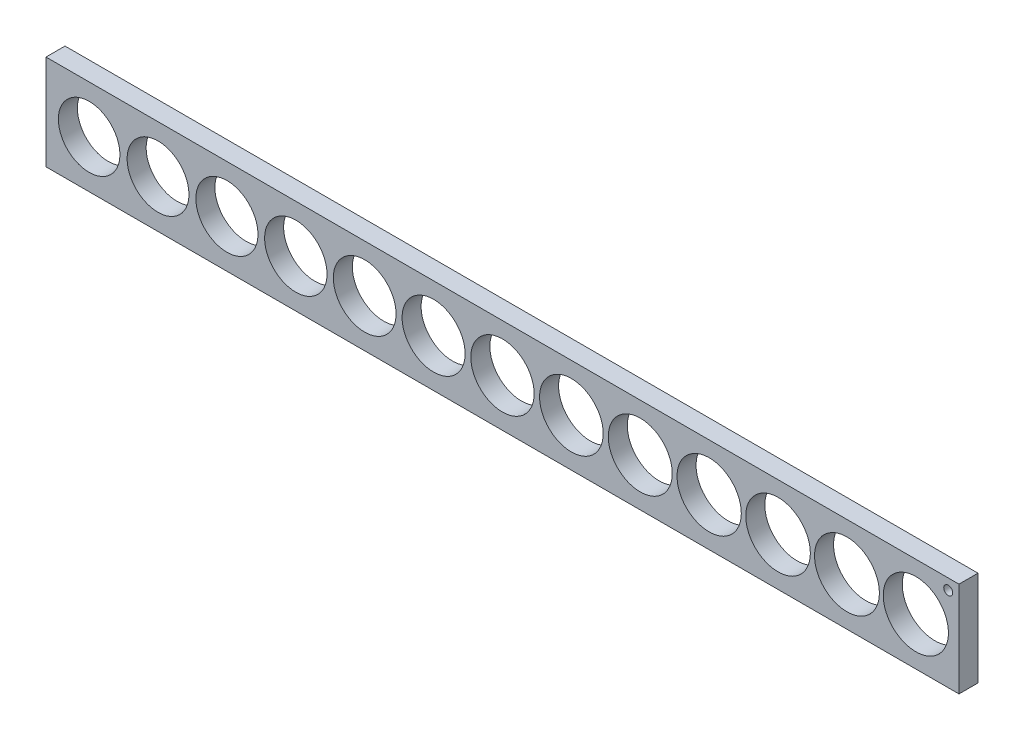
SolidWorks part; units mm, degrees
material "Custom Plastic"
ref_plane "X-Y Datum" through (0, 0, 0) normal (0, 0, 1) x (1, 0, 0)
ref_plane "X-Z Datum" through (0, 0, 0) normal (0, 1, 0) x (1, 0, 0)
ref_plane "Y-Z Datum" through (0, 0, 0) normal (1, 0, 0) x (0, 0, -1)
sketch "Sketch1" plane through (0, 0, 0) normal (0, 0, 1) x (1, 0, 0)
  line L0 (-152.4, 0) -> (152.4, 0) construction
  line L1 (-152.4, 15.875) -> (152.4, 15.875)
  line L2 (-152.4, 15.875) -> (-152.4, -15.875)
  line L3 (-152.4, -15.875) -> (152.4, -15.875)
  line L4 (152.4, 15.875) -> (152.4, -15.875)
  line L5 (-152.4, 15.875) -> (152.4, -15.875) construction
  line L6 (-152.4, -15.875) -> (152.4, 15.875) construction
  line L7 (0, -55) -> (0, 55) construction
  line L8 (148.8079, 12.2829) -> (152.4, 15.875) construction
  circle A0 centre (0, 0) radius 10.575
  circle A1 centre (23, 0) radius 10.575 construction
  circle A2 centre (46, 0) radius 10.575 construction
  circle A3 centre (69, 0) radius 10.575 construction
  circle A4 centre (92, 0) radius 10.575 construction
  circle A5 centre (115, 0) radius 10.575 construction
  circle A7 centre (-115, 0) radius 10.575 construction
  circle A8 centre (-92, 0) radius 10.575 construction
  circle A9 centre (-69, 0) radius 10.575 construction
  circle A10 centre (-46, 0) radius 10.575 construction
  circle A11 centre (-23, 0) radius 10.575 construction
  circle A12 centre (23, 0) radius 10.6258
  circle A13 centre (46, 0) radius 10.6766
  circle A14 centre (69, 0) radius 10.7274
  circle A15 centre (92, 0) radius 10.7782
  circle A16 centre (115, 0) radius 10.829
  circle A17 centre (138, 0) radius 10.575 construction
  circle A18 centre (-138, 0) radius 10.575 construction
  circle A19 centre (138, 0) radius 10.8798
  circle A20 centre (-138, 0) radius 10.2702
  circle A21 centre (-115, 0) radius 10.321
  circle A22 centre (-92, 0) radius 10.3718
  circle A23 centre (-69, 0) radius 10.4226
  circle A24 centre (-46, 0) radius 10.4734
  circle A25 centre (-23, 0) radius 10.5242
  circle A26 centre (148.8079, 12.2829) radius 1.5
  point P0 (0, 0)
  point P62 (149.2098, 12.6848)
  dimension "D1" = 21.15
  dimension "D22" = 3
  dimension "D23" = 20.5404
  dimension "D24" = 20.642
  dimension "D25" = 20.7436
  dimension "D26" = 20.8452
  dimension "D27" = 20.9468
  dimension "D28" = 21.0484
  dimension "D29" = 21.2516
  dimension "D30" = 21.3532
  dimension "D31" = 21.4548
  dimension "D32" = 21.5564
  dimension "D33" = 21.658
  dimension "D34" = 21.7596
  dimension "D2" = 304.8
  dimension "D3" = 31.75
  dimension "D4" = 23
  dimension "D5" = 23
  dimension "D6" = 23
  dimension "D7" = 23
  dimension "D8" = 23
  dimension "D14" = 23
  dimension "D35" = 45
  dimension "D36" = 5.08
  dimension "D9" = 0.0508
  dimension "D10" = 0.1016
  dimension "D11" = 0.1524
  dimension "D12" = 0.2032
  dimension "D13" = 0.254
  dimension "D15" = 0.3048
  dimension "D16" = 0.3048
  dimension "D17" = 0.254
  dimension "D18" = 0.2032
  dimension "D19" = 0.1524
  dimension "D20" = 0.1016
  dimension "D21" = 0.0508
extrude "Boss-Extrude1" add sketch "Sketch1" along normal blind 6.35
